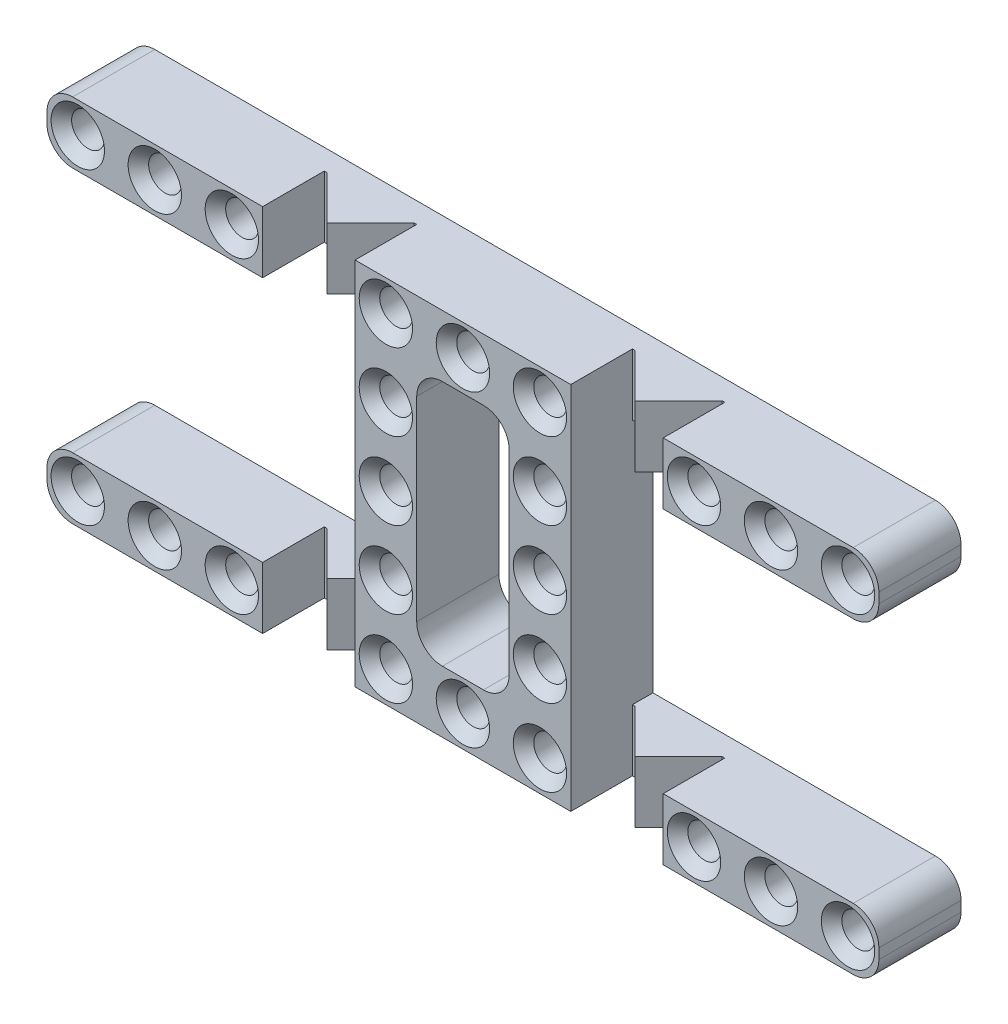
SolidWorks part; units mm, degrees
ref_plane "Front Plane" through (0, 0, 0) normal (0, 0, 1) x (1, 0, 0)
ref_plane "Top Plane" through (0, 0, 0) normal (0, 1, 0) x (1, 0, 0)
ref_plane "Right Plane" through (0, 0, 0) normal (1, 0, 0) x (0, 0, -1)
sketch "Sketch1" plane through (0, 0, 0) normal (0, 0, 1) x (1, 0, 0)
  line L1 (-0.5, 3) -> (15.5, 3)
  line L2 (-3, 0.5) -> (-3, -0.5)
  line L3 (-0.5, -3) -> (15.5, -3)
  line L4 (18, 0.5) -> (18, -0.5)
  circle A0 centre (0, 0) radius 1.6
  circle A1 centre (15, 0) radius 1.6
  arc A2 (15.5, -3) -> (18, -0.5) centre (15.5, -0.5) ccw
  arc A3 (15.5, 3) -> (18, 0.5) centre (15.5, 0.5) cw
  arc A4 (-3, -0.5) -> (-0.5, -3) centre (-0.5, -0.5) ccw
  arc A5 (-0.5, 3) -> (-3, 0.5) centre (-0.5, 0.5) ccw
  point P13 (18, 3)
  point P18 (-3, 3)
  dimension "D1" = 3.2
  dimension "D5" = 3.2
  dimension "D6" = 3
  dimension "D9" = 2.5
  dimension "D2" = 3
  dimension "D3" = 3
  dimension "D4" = 3
  dimension "D7" = 3
  dimension "D8" = 21
extrude "Boss-Extrude1" add sketch "Sketch1" along normal blind 8
sketch "Sketch2" plane through (0, -3, 0) normal (0, -1, 0) x (1, 0, 0)
  line L0 (18, 8) -> (18, 0) construction
  line L1 (3, 10.1997) -> (12, 10.1997)
  line L2 (3, 10.1997) -> (3, 2)
  line L3 (3, 2) -> (12, 2)
  line L4 (12, 10.1997) -> (12, 2)
  line L5 (-3, 8) -> (-3, 0) construction
  line L6 (-0.5, 0) -> (15.5, 0) construction
  dimension "D1" = 6
  dimension "D2" = 6
  dimension "D3" = 2
extrude "Cut-Extrude1" cut sketch "Sketch2" against normal blind 8
sketch "Sketch3" plane through (0, -3, 0) normal (0, -1, 0) x (1, 0, 0)
  line L0 (3.2574, 2) -> (7.5, 6.2426)
  line L1 (3, 2) -> (12, 2) construction
  line L2 (7.5, 6.2426) -> (11.7426, 2)
  line L3 (11.7426, 2) -> (3.2574, 2)
  line L5 (-0.5, 0) -> (15.5, 0) construction
  point P10 (7.5, 0)
  dimension "D1" = 90
  dimension "D2" = 45
  dimension "D3" = 6
extrude "Boss-Extrude2" add sketch "Sketch3" against normal up to surface (6 mm away) up to face at (7.5, 3, 4.5)
sketch "Sketch4" plane through (0, 0, 0) normal (0, 0, -1) x (-1, 0, 0)
  line L0 (-3, 3) -> (0.5, 3) construction
  line L1 (0.5, 3) -> (15.5, 3)
  line L3 (0.5, -3) -> (15.5, -3)
  line L4 (18, 0.5) -> (18, -0.5)
  line L5 (-7.5, 3) -> (-7.5, 8.5491) construction
  line L6 (-33, 0.5) -> (-33, -0.5)
  line L7 (-15.5, -3) -> (-30.5, -3)
  line L8 (-15.5, 3) -> (-30.5, 3)
  arc A0 (3, 0.5) -> (0.5, 3) centre (0.5, 0.5) ccw construction
  circle A1 centre (7.5, 0) radius 1.6
  arc A2 (15.5, -3) -> (18, -0.5) centre (15.5, -0.5) ccw
  arc A3 (15.5, 3) -> (18, 0.5) centre (15.5, 0.5) cw
  circle A4 centre (-30, 0) radius 1.6
  arc A5 (-30.5, 3) -> (-33, 0.5) centre (-30.5, 0.5) ccw
  circle A8 centre (15, 0) radius 1.6
  arc A9 (-30.5, -3) -> (-33, -0.5) centre (-30.5, -0.5) cw
  circle A10 centre (-22.5, 0) radius 1.6
  arc M4 (-18, -0.5) -> (-15.5, -3) centre (-15.5, -0.5) ccw
  arc M6 (0.5, -3) -> (3, -0.5) centre (0.5, -0.5) ccw
  line M7 (3, -0.5) -> (3, 0.5)
  arc M8 (3, 0.5) -> (0.5, 3) centre (0.5, 0.5) ccw
  arc M10 (-15.5, 3) -> (-18, 0.5) centre (-15.5, 0.5) ccw
  line M11 (-18, 0.5) -> (-18, -0.5)
  dimension "D1" = 3.2
  dimension "D3" = 2.5
  dimension "D2" = 7.5
  dimension "D4" = 2
  dimension "D5" = 3
extrude "Boss-Extrude3" add sketch "Sketch4" against normal blind 8 contours A3 L1 L3 A2 L4 A1 M8 M7 M6 | M4 M11 M10 region at (-9.7924, 0, 0) region at (24.7924, 0, 0)
sketch "Sketch5" plane through (0, 0, 8) normal (0, 0, 1) x (1, 0, 0)
  line L1 (3, 3) -> (-21.5999, 3)
  line L2 (3, 3) -> (3, -8.8412)
  line L3 (3, -8.8412) -> (-21.5999, -8.8412)
  line L4 (-21.5999, 3) -> (-21.5999, -8.8412)
extrude "Cut-Extrude2" cut sketch "Sketch5" against normal blind 10
sketch "Sketch6" plane through (0, 0, 0) normal (0, 0, -1) x (-1, 0, 0)
  line L0 (3, -3) -> (3, -27)
  line L5 (-3, 3) -> (18, 3)
  line L6 (-3, 3) -> (-3, -33)
  line L7 (-3, -33) -> (18, -33)
  line L8 (18, 3) -> (18, -33)
  line L9 (3, -27) -> (12, -27)
  line L10 (12, -3) -> (12, -27)
  line L11 (3, -3) -> (12, -3)
  line L12 (12, -15) -> (6.5478, -15) construction
  line L13 (7.5, -3) -> (7.5, -19.2238) construction
  circle A0 centre (0, 0) radius 1.6
  circle A1 centre (7.5, 0) radius 1.6
  circle A2 centre (15, 0) radius 1.6
  circle A3 centre (0, -7.5) radius 1.6
  circle A4 centre (0, -15) radius 1.6
  circle A5 centre (0, -22.5) radius 1.6
  circle A6 centre (0, -30) radius 1.6
  circle A7 centre (15, -30) radius 1.6
  circle A8 centre (7.5, -30) radius 1.6
  circle A9 centre (15, -22.5) radius 1.6
  circle A10 centre (15, -15) radius 1.6
  circle A11 centre (15, -7.5) radius 1.6
  dimension "D2" = 3.2
  dimension "D5" = 3
  dimension "D6" = 3
  dimension "D1" = 6
  dimension "D3" = 3
  dimension "D4" = 5
extrude "Boss-Extrude4" add sketch "Sketch6" against normal blind 8
pattern_linear "LPattern1" count 2 spacing 30 along (0, -1, 0) of "Boss-Extrude1", "Boss-Extrude3", "Boss-Extrude2", "Cut-Extrude1"
ref_plane "Plane1" through (-7.5, 0, 0) normal (-1, 0, 0) x (0, 0, 1)
mirror "Mirror1" about plane through (-7.5, 0, 0) normal (-1, 0, 0) of "Boss-Extrude4", "LPattern1", "Cut-Extrude1", "Boss-Extrude2", "Boss-Extrude1", "Boss-Extrude3"
fillet "Fillet1" radius 2.5 4 edges at (-3, -27, 4) (-12, -27, 4) (-12, -3, 4) (-3, -3, 4)
chamfer "Chamfer1" distance 1 angle 45 48 edges at (28.4, 0, 0) (28.4, 0, 8) (20.9, 0, 0) (20.9, 0, 8) (16.6, 0, 0) (16.6, 0, 8) (28.4, -30, 0) (28.4, -30, 8) (20.9, -30, 0) (20.9, -30, 8) (16.6, -30, 0) (16.6, -30, 8) (-43.4, -30, 0) (-43.4, -30, 8) (-35.9, -30, 0) (-35.9, -30, 8) (-31.6, -30, 0) (-31.6, -30, 8) (-13.4, -22.5, 0) (-13.4, -22.5, 8) (-13.4, -30, 0) (-13.4, -30, 8) (-5.9, -30, 0) (-5.9, -30, 8) (-1.6, -30, 0) (-1.6, -30, 8) (-1.6, -22.5, 0) (-1.6, -22.5, 8) (-1.6, -15, 0) (-1.6, -15, 8) (-13.4, -15, 0) (-13.4, -15, 8) (-13.4, -7.5, 0) (-13.4, -7.5, 8) (-1.6, -7.5, 0) (-1.6, -7.5, 8) (-1.6, 0, 0) (-1.6, 0, 8) (-9.1, 0, 0) (-9.1, 0, 8) (-16.6, 0, 0) (-16.6, 0, 8) (-31.6, 0, 0) (-31.6, 0, 8) (-35.9, 0, 0) (-35.9, 0, 8) (-43.4, 0, 0) (-43.4, 0, 8)
